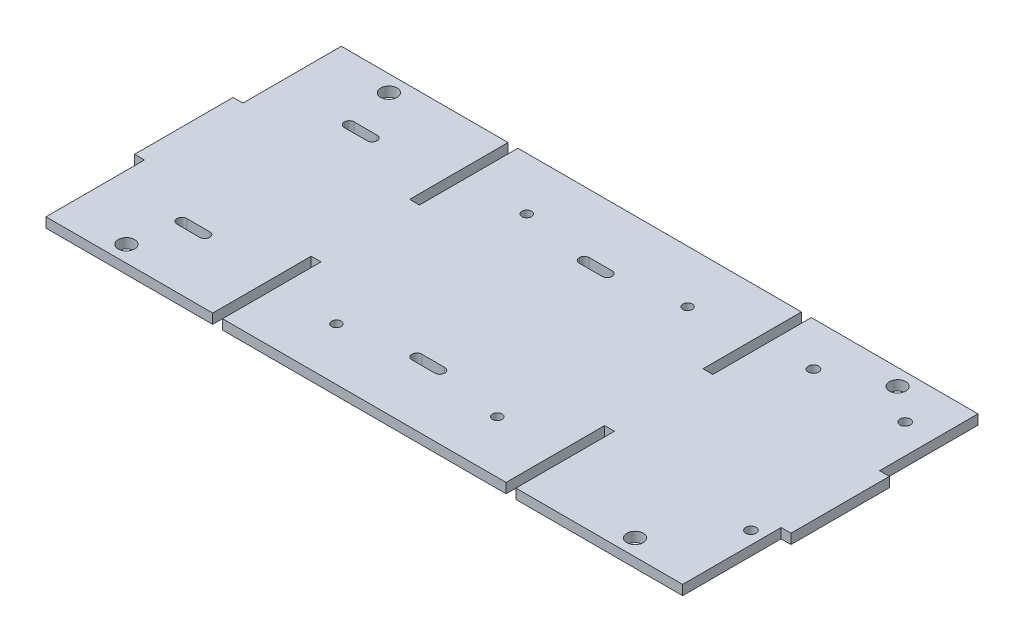
SolidWorks part; units mm, degrees
ref_plane "Front Plane" through (0, 0, 0) normal (0, 0, 1) x (1, 0, 0)
ref_plane "Top Plane" through (0, 0, 0) normal (0, 1, 0) x (1, 0, 0)
ref_plane "Right Plane" through (0, 0, 0) normal (1, 0, 0) x (0, 0, -1)
sketch "Sketch1" plane through (0, 0, 0) normal (0, 1, 0) x (1, 0, 0)
  line L1 (-100, -45) -> (100, -45)
  line L2 (-100, -45) -> (-100, 45)
  line L3 (-100, 45) -> (100, 45)
  line L4 (100, -45) -> (100, 45)
  line L5 (-100, -45) -> (100, 45) construction
  line L6 (-100, 45) -> (100, -45) construction
  point P0 (0, 0)
  dimension "D1" = 200
  dimension "D2" = 90
extrude "Boss-Extrude1" add sketch "Sketch1" along normal blind 3
sketch "Sketch2" plane through (0, 3, 0) normal (0, 1, 0) x (1, 0, 0)
  line L0 (-97, 15) -> (-97, -15) construction
  line L1 (-100, 45) -> (-97, 45)
  line L2 (-100, 45) -> (-100, 15)
  line L3 (-100, 15) -> (-97, 15)
  line L4 (-97, 45) -> (-97, 15)
  line L5 (-100, -45) -> (-97, -45)
  line L6 (-100, -45) -> (-100, -15)
  line L7 (-100, -15) -> (-97, -15)
  line L8 (-97, -45) -> (-97, -15)
  dimension "D1" = 3
extrude "Cut-Extrude1" cut sketch "Sketch2" against normal through all
mirror "Mirror1" about plane through (0, 0, 0) normal (1, 0, 0) of "Cut-Extrude1"
sketch "Sketch3" plane through (0, 3, 0) normal (0, 1, 0) x (1, 0, 0)
  line L0 (97, 45) -> (-97, 45) construction
  line L1 (46.2, 45) -> (43.2, 45)
  line L2 (46.2, 45) -> (46.2, 15)
  line L3 (46.2, 15) -> (43.2, 15)
  line L4 (43.2, 45) -> (43.2, 15)
  line L5 (-97, -45) -> (97, -45) construction
  line L6 (46.2, -45) -> (43.2, -45)
  line L7 (46.2, -45) -> (46.2, -15)
  line L8 (46.2, -15) -> (43.2, -15)
  line L9 (43.2, -45) -> (43.2, -15)
  line L10 (46.2, -15) -> (46.2, 15) construction
  line L11 (43.2, 12.5) -> (43.2, -12.5) construction
  dimension "D1" = 3
extrude "Cut-Extrude2" cut sketch "Sketch3" against normal through all
mirror "Mirror2" about plane through (0, 0, 0) normal (1, 0, 0) of "Cut-Extrude2"
sketch "Sketch4" plane through (0, 0, 0) normal (0, -1, 0) x (1, 0, 0)
  line L0 (-97, 45) -> (-46.2, 45) construction
  line L1 (-5, 27) -> (5, 27)
  line L2 (-5, 27) -> (-5, 24)
  line L3 (-5, 24) -> (5, 24)
  line L4 (5, 27) -> (5, 24)
  line L5 (-5, 27) -> (5, 24) construction
  line L6 (-5, 24) -> (5, 27) construction
  line L7 (-5, -24) -> (5, -24)
  line L12 (-5, -24) -> (-5, -27)
  line L13 (-5, -27) -> (5, -27)
  line L14 (5, -24) -> (5, -27)
  line L15 (-5, -24) -> (5, -27) construction
  line L16 (-5, -27) -> (5, -24) construction
  line L17 (-76.6, 27) -> (-66.6, 27)
  line L18 (-76.6, 27) -> (-76.6, 24)
  line L19 (-76.6, 24) -> (-66.6, 24)
  line L20 (-66.6, 27) -> (-66.6, 24)
  line L21 (-76.6, 27) -> (-66.6, 24) construction
  line L22 (-76.6, 24) -> (-66.6, 27) construction
  line L23 (-66.6, -24) -> (-76.6, -24)
  line L24 (-66.6, -24) -> (-66.6, -27)
  line L25 (-66.6, -27) -> (-76.6, -27)
  line L26 (-76.6, -24) -> (-76.6, -27)
  line L27 (-66.6, -24) -> (-76.6, -27) construction
  line L28 (-66.6, -27) -> (-76.6, -24) construction
  line L29 (-97, 23) -> (35, 23) construction
  line L30 (35, -23) -> (-97, -23) construction
  circle A0 centre (-24.5, 29) radius 1.45 construction
  circle A1 centre (24.5, 29) radius 1.45 construction
  circle A2 centre (24.5, -29) radius 1.45 construction
  circle A3 centre (-24.5, -29) radius 1.45 construction
  circle A4 centre (-24.5, 29) radius 1.45
  circle A5 centre (24.5, 29) radius 1.45
  circle A6 centre (24.5, -29) radius 1.45
  circle A7 centre (-24.5, -29) radius 1.45
  circle A9 centre (93.13, 20.32) radius 1.5875 construction
  circle A10 centre (60.11, -31.75) radius 1.5875 construction
  circle A11 centre (88.05, -31.75) radius 1.5875 construction
  circle A13 centre (93.13, 20.32) radius 1.5875
  circle A14 centre (60.11, -31.75) radius 1.5875
  circle A15 centre (88.05, -31.75) radius 1.5875
  point P12 (0, 25.5)
  point P26 (0, -25.5)
  point P31 (-71.6, 25.5)
  point P36 (-71.6, -25.5)
  point P43 (-71.6, 45)
  dimension "D1" = 3
  dimension "D2" = 1
  dimension "D3" = 1
  dimension "D4" = 10
extrude "Cut-Extrude3" cut sketch "Sketch4" against normal through all
fillet "Fillet1" radius 1.5 16 edges at (-5, 1.5, -27) (-5, 1.5, -24) (5, 1.5, -24) (5, 1.5, -27) (-5, 1.5, 24) (-5, 1.5, 27) (5, 1.5, 27) (5, 1.5, 24) (-76.6, 1.5, 24) (-76.6, 1.5, 27) (-66.6, 1.5, 27) (-66.6, 1.5, -24) (-66.6, 1.5, -27) (-76.6, 1.5, -27) (-76.6, 1.5, -24) (-66.6, 1.5, 24)
sketch "Sketch5" plane through (0, 3, 0) normal (0, 1, 0) x (1, 0, 0)
  line L1 (-77.5, -40) -> (77.5, -40) construction
  line L2 (-77.5, -40) -> (-77.5, 40) construction
  line L3 (-77.5, 40) -> (77.5, 40) construction
  line L4 (77.5, -40) -> (77.5, 40) construction
  line L5 (-77.5, -40) -> (77.5, 40) construction
  line L6 (-77.5, 40) -> (77.5, -40) construction
  circle A0 centre (-77.5, 40) radius 2.5
  circle A1 centre (77.5, 40) radius 2.5
  circle A2 centre (77.5, -40) radius 2.5
  circle A3 centre (-77.5, -40) radius 2.5
  point P0 (0, 0)
  dimension "D1" = 5
  dimension "D2" = 80
  dimension "D3" = 155
extrude "Cut-Extrude4" cut sketch "Sketch5" against normal through all
